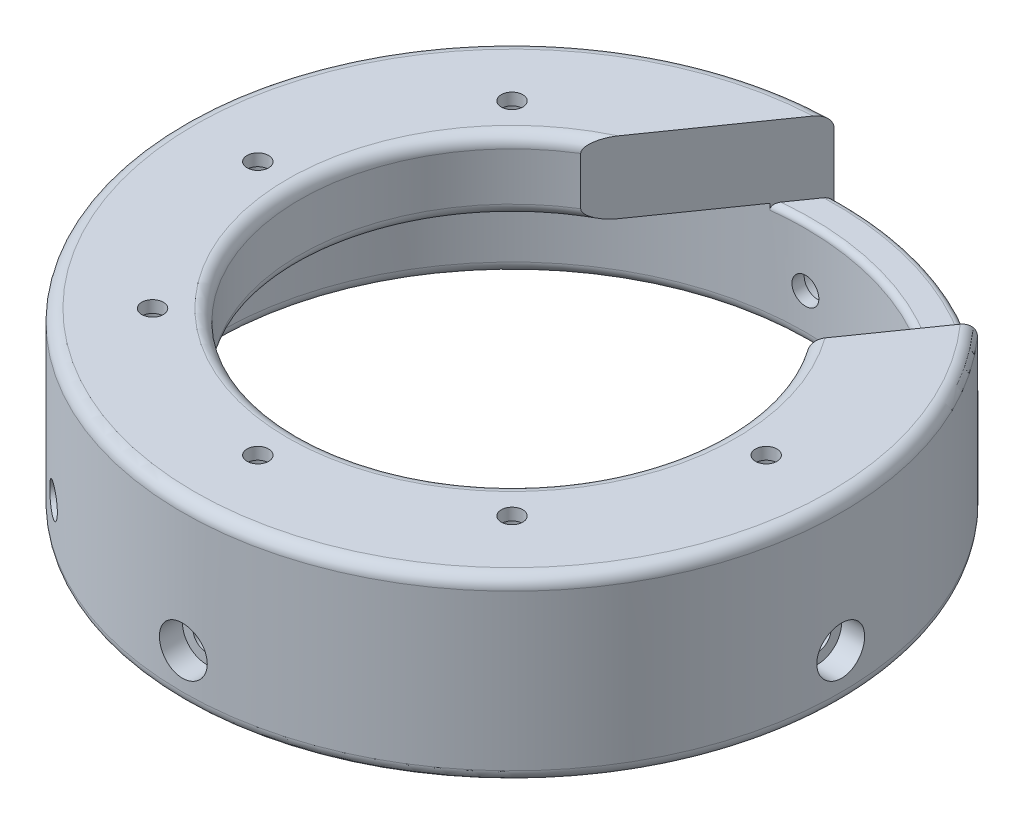
SolidWorks part; units mm, degrees
material "Custom PLA"
ref_plane "Front Plane" through (0, 0, 0) normal (0, 0, 1) x (1, 0, 0)
ref_plane "Top Plane" through (0, 0, 0) normal (0, 1, 0) x (1, 0, 0)
ref_plane "Right Plane" through (0, 0, 0) normal (1, 0, 0) x (0, 0, -1)
sketch "Sketch1" plane through (0, 0, 0) normal (1, 0, 0) x (0, 0, -1)
  line L0 (0, 0) -> (0, 12)
  line L1 (0, 12) -> (55.1, 12)
  line L2 (55.1, 12) -> (55.1, -18)
  line L3 (55.1, -18) -> (49.1, -18)
  line L4 (49.1, -18) -> (49.1, 0)
  line L5 (49.1, 0) -> (0, 0)
  dimension "D1" = 12
  dimension "D2" = 6
  dimension "D3" = 18
  dimension "D4" = 49.1
revolve "Revolve1" add sketch "Sketch1" angle 360 about L0
ref_plane "Plane3" through (0, 0, -55.1) normal (0, 0, -1) x (-1, 0, 0)
sketch "Sketch2" plane through (0, 12, 0) normal (0, 1, 0) x (1, 0, 0)
  circle A0 centre (0, 0) radius 42.5 construction
  circle A1 centre (0, 42.5) radius 1.8
  dimension "D1" = 85
  dimension "D2" = 3.6
extrude "Cut-Extrude1" cut sketch "Sketch2" against normal up to next contours A1
pattern_circular "CirPattern1" count 8 over 360 about axis through (0, 12, 0) along (0, -1, 0) of "Cut-Extrude1"
sketch "Sketch3" plane through (0, 12, 0) normal (0, 1, 0) x (1, 0, 0)
  circle A0 centre (0, 0) radius 35.5
  dimension "D1" = 71
extrude "Cut-Extrude2" cut sketch "Sketch3" against normal up to next
ref_plane "Plane1" through (0, 0, 55.1) normal (0, 0, 1) x (1, 0, 0)
sketch "Sketch6" plane through (0, 0, 55.1) normal (0, 0, 1) x (1, 0, 0)
  line L0 (-55.1, -10) -> (55.1, -10) construction
  line L1 (-55.1, 12) -> (-55.1, -18) construction
  line L2 (55.1, -18) -> (55.1, 12) construction
  line L3 (-55.1, -18) -> (55.1, -18) construction
  line L4 (0, 12) -> (0, -18) construction
  line L5 (1.8, 12) -> (-1.8, 12) construction
  line L6 (-55.1, 0) -> (55.1, 0) construction
  circle A0 centre (0, -10) radius 3.3
  point P12 (0, -10)
  dimension "D2" = 6.6
  dimension "D1" = 10
hole_wizard "CBORE for M4 SHCS1" positions "Sketch6" profile "Sketch7" counterbore size "M4" standard "ANSI Metric" end condition up to next
sketch "Sketch7" plane through (0, -10, 55.1) normal (1, 0, 0) x (0, -1, 0)
  line L0 (0, 0) -> (0, 6)
  line L1 (0, 6) -> (2.25, 6)
  line L3 (2.25, 6) -> (2.25, 4)
  line L4 (2.25, 4) -> (4, 4)
  line L5 (4, 4) -> (4, 0)
  line L7 (4, 0) -> (0, 0)
  line L11 (0, -6.35) -> (0, 107.95) construction
  dimension "Thru Hole Dia." = 4.5
  dimension "Thru Hole Depth" = 6
  dimension "C'Bore Dia." = 8
  dimension "C'Bore Depth" = 4
mirror "Mirror2" about plane through (0, 0, 0) normal (0, 0, 1) of "CBORE for M4 SHCS1"
ref_plane "Plane2" through (-55.1, 0, 0) normal (-1, 0, 0) x (0, 0, 1)
sketch "Sketch8" plane through (-55.1, 0, 0) normal (-1, 0, 0) x (0, 0, 1)
  line L0 (-54.1, -10) -> (54.1, -10) construction
  line L3 (-55.1, -18) -> (55.1, -18) construction
  line L4 (0, 12) -> (0, -18) construction
  line L5 (55.1, 12) -> (-55.1, 12) construction
  line L6 (-54.1, 0) -> (55.1, 0) construction
  line L7 (55.1, -6) -> (55.1, 12) construction
  point P11 (0, -10)
  dimension "D1" = 10
hole_wizard "CBORE for M4 SHCS2" positions "Sketch8" profile "Sketch9" counterbore size "M4" standard "ANSI Metric" end condition up to next
sketch "Sketch9" plane through (-55.1, -10, 0) normal (0, 1, 0) x (0, 0, 1)
  line L0 (0, 0) -> (0, 6)
  line L1 (0, 6) -> (2.25, 6)
  line L3 (2.25, 6) -> (2.25, 4)
  line L4 (2.25, 4) -> (4, 4)
  line L5 (4, 4) -> (4, 0)
  line L7 (4, 0) -> (0, 0)
  line L11 (0, -6.35) -> (0, 107.95) construction
  dimension "Thru Hole Dia." = 4.5
  dimension "Thru Hole Depth" = 6
  dimension "C'Bore Dia." = 8
  dimension "C'Bore Depth" = 4
sketch "Sketch10" plane through (0, 0, -55.1) normal (0, 0, 1) x (1, 0, 0)
  line L0 (35.5, 12) -> (-35.5, 12) construction
  line L1 (-5, 12) -> (30, 12)
  line L2 (-5, 12) -> (-5, 0)
  line L3 (-5, 0) -> (30, 0)
  line L4 (30, 12) -> (30, 0)
  line L5 (0, 0) -> (0, 12) construction
  line L6 (1.8, 12) -> (-1.8, 12) construction
  dimension "D1" = 5
  dimension "D2" = 35
  dimension "D3" = 12
extrude "Cut-Extrude3" [suppressed] cut sketch "Sketch10" along normal blind 45
mirror "Mirror3" about plane through (0, 0, 0) normal (1, 0, 0) of "CBORE for M4 SHCS2"
sketch3d "3DSketch1"
  line L0 (30.052, -10, -30.052) -> (0, -10, -51.1)
  line L3 (0, -10, -49.1) -> (0, -10, -51.1) construction
  line L4 (30.052, 12, -30.052) -> (30.052, -22.1775, -30.052) construction
  line L5 (30.052, 0, -30.052) -> (30.052, 12, -30.052) construction
ref_plane "Slay Plane" through (24.0112, 0, -34.2829) normal (0.5737, 0, -0.8191) x (-0.8191, 0, -0.5737)
sketch "Sketch11" plane through (0, 0, 0) normal (0, -1, 0) x (1, 0, 0)
  line L0 (0, 64.2941) -> (0, -73.7272) construction
  circle A0 centre (0, 0) radius 42.5 construction
  circle A1 centre (0, 42.5) radius 3.2
  dimension "D1" = 85
  dimension "D2" = 6.4
extrude "Cut-Extrude4" cut sketch "Sketch11" against normal blind 10 contours A1
pattern_circular "CirPattern6" count 8 over 360 about axis through (0, 0, 0) along (0, 1, 0) of "Cut-Extrude4"
fillet "Fillet1" radius 2 5 edges at (0, 0, -35.5) (0, 12, 35.5) (0, -18, -49.1) (0, -18, -55.1) (0, 12, -55.1)
fillet "Fillet2" [suppressed] radius 2
fillet "Fillet4" [suppressed] radius 1
fillet "Fillet5" [suppressed] radius 1
ref_plane "Plane4" through (0, 0, -55.1) normal (0, 0, -1) x (-1, 0, 0)
ref_plane "Plane5" through (55.1, 0, 0) normal (1, 0, 0) x (0, 0, -1)
ref_plane "Plane6" through (31.6094, 0, -45.1315) normal (0.5737, 0, -0.8191) x (-0.8191, 0, -0.5737)
sketch "Sketch13" plane through (24.0112, 0, -34.2829) normal (0.5737, 0, -0.8191) x (-0.8191, 0, -0.5737)
  line L0 (-7.3751, -10) -> (29.3147, -10) construction
sketch "Sketch14" plane through (95.4625, 0, 15.7604) normal (-0.5737, 0, 0.8191) x (0.8191, 0, 0.5737)
  line L0 (-49.7332, 12) -> (-124.7332, 12) construction
  line L1 (-119.8581, 12) -> (-74.8581, 12)
  line L2 (-119.8581, 12) -> (-119.8581, 0)
  line L3 (-119.8581, 0) -> (-74.8581, 0)
  line L4 (-74.8581, 12) -> (-74.8581, 0)
  line L6 (-79.8581, 12) -> (-79.8581, -22.1775) construction
  dimension "D1" = 5
  dimension "D2" = 45
  dimension "D3" = 12
extrude "Cut-Extrude5" cut sketch "Sketch14" against normal blind 30 and the other way blind 30 contours L1 L4 L3 L2
sketch "Sketch15" plane through (31.6094, 0, -45.1315) normal (0.5737, 0, -0.8191) x (-0.8191, 0, -0.5737)
  line L0 (0, 0) -> (0, -18) construction
  line L1 (-55.1, -18) -> (55.1, -18) construction
  line L2 (-23.6977, -9) -> (23.6977, -9) construction
  circle A0 centre (0, -9) radius 2.58
  point P7 (0, -9)
  point P8 (0, -9)
  dimension "D1" = 5.16
extrude "Cut-Extrude6" cut sketch "Sketch15" against normal blind 3.8
ref_plane "Plane7" through (0, 0, 0) normal (0.5737, 0, -0.8191) x (-0.8191, 0, -0.5737)
mirror "Mirror4" about plane through (0, 0, 0) normal (0.5737, 0, -0.8191) of "Cut-Extrude6"
fillet "Fillet11" [suppressed] radius 1
sketch3d "3DSketch2"
  line L0 (29.4294, -9, -42.019) -> (31.5747, -9, -45.082) construction
  line L1 (0, -10, -49.1) -> (0, -10, -51.1) construction
  line L2 (29.4294, -9, -42.019) -> (0, -10, -67.8946)
  line L3 (0, -10, -51.1) -> (0, -10, -55.1) construction
  point P0 (35.7899, -9.1145, -36.7593)
  point P1 (29.4294, -9, -42.019)
  point P2 (0, -10, -51.1)
  point P11 (14.7147, -9.5, -54.9568)
  point P12 (14.7147, -9.5, -54.9568)
fillet "Fillet12" radius 1 2 edges at (17.9836, 0, -45.6881) (21.8326, 0, -50.59)
